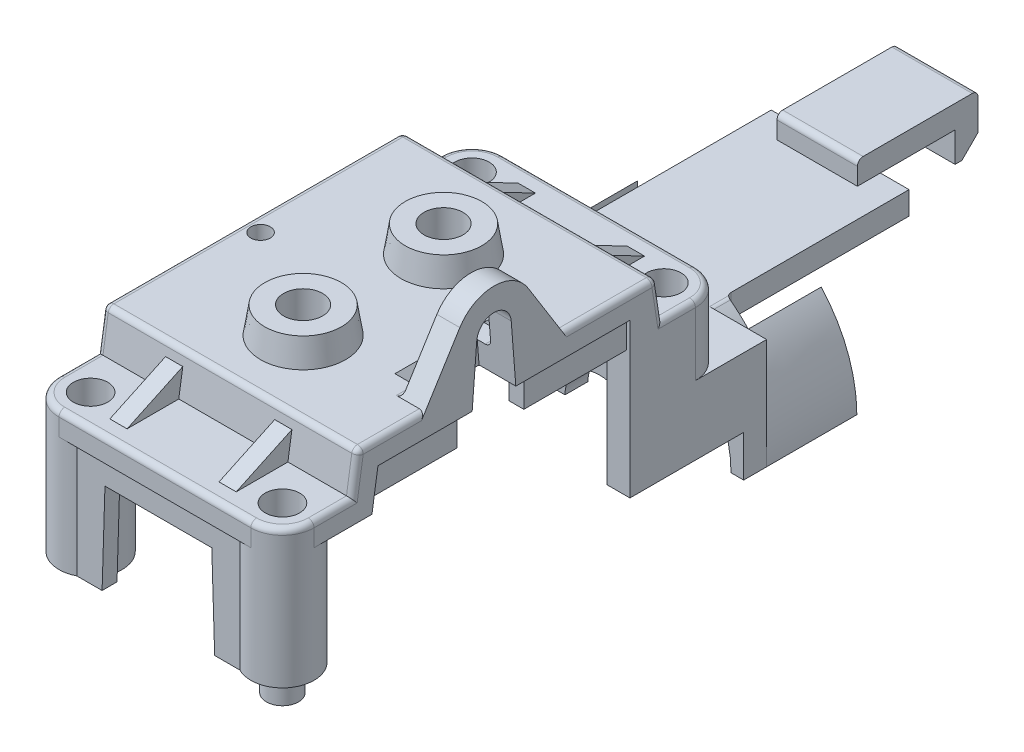
SolidWorks part; units mm, degrees
ref_plane "Front Plane" through (0, 0, 0) normal (0, 0, 1) x (1, 0, 0)
ref_plane "Top Plane" through (0, 0, 0) normal (0, 1, 0) x (1, 0, 0)
ref_plane "Right Plane" through (0, 0, 0) normal (1, 0, 0) x (0, 0, -1)
sketch "Sketch1" plane through (0, 0, 0) normal (0, 1, 0) x (1, 0, 0)
  line L1 (8.35, -16.6) -> (-8.35, -16.6) construction
  line L2 (8.35, -16.6) -> (8.35, 16.6) construction
  line L3 (8.35, 16.6) -> (-8.35, 16.6) construction
  line L4 (-8.35, -16.6) -> (-8.35, 16.6) construction
  line L5 (8.35, -16.6) -> (-8.35, 16.6) construction
  line L6 (8.35, 16.6) -> (-8.35, -16.6) construction
  circle A0 centre (-8.35, 16.6) radius 2.75
  circle A1 centre (8.35, 16.6) radius 2.75
  circle A2 centre (-8.35, -16.6) radius 2.75
  circle A3 centre (8.35, -16.6) radius 2.75
  point P0 (0, 0)
  dimension "D2" = 5.5
  dimension "D1" = 33.2
  dimension "D3" = 16.7
extrude "Boss-Extrude1" add sketch "Sketch1" along normal blind 10
sketch "Sketch2" plane through (0, 10, 0) normal (0, 1, 0) x (1, 0, 0)
  line L0 (-11.1, 16.6) -> (11.1, 16.6)
  line L1 (-11.1, -16.6) -> (11.1, -16.6)
  line L2 (-11.1, -16.6) -> (-11.1, -11.25)
  line L3 (-11.1, -11.25) -> (11.1, -11.25)
  line L4 (11.1, -16.6) -> (11.1, -11.25)
  line L5 (8.35, -19.35) -> (-8.35, -19.35)
  line L6 (8.35, -19.35) -> (8.35, -16.6)
  line L7 (8.35, -16.6) -> (-8.35, -16.6)
  line L8 (-8.35, -19.35) -> (-8.35, -16.6)
  line L9 (-11.1, 16.6) -> (-11.1, 11.75)
  line L10 (11.1, 16.6) -> (11.1, 11.75)
  line L11 (-11.1, 11.75) -> (11.1, 11.75)
  line L12 (-8.35, 19.35) -> (8.35, 19.35)
  line L13 (-8.35, 19.35) -> (-8.35, 16.6)
  line L14 (8.35, 19.35) -> (8.35, 16.6)
  line L15 (-8.35, 16.6) -> (8.35, 16.6)
  circle A0 centre (-8.35, -16.6) radius 2.75 construction
  circle A1 centre (8.35, -16.6) radius 2.75 construction
  arc A2 (-8.35, -19.35) -> (-11.1, -16.6) centre (-8.35, -16.6) cw
  arc A3 (8.35, -19.35) -> (11.1, -16.6) centre (8.35, -16.6) ccw
  circle A4 centre (-8.35, 16.6) radius 2.75 construction
  circle A5 centre (8.35, 16.6) radius 2.75 construction
  arc A6 (8.35, 19.35) -> (11.1, 16.6) centre (8.35, 16.6) cw
  arc A7 (-11.1, 16.6) -> (-8.35, 19.35) centre (-8.35, 16.6) cw
  point P32 (-8.35, 13.85)
  circle M5 centre (8.35, -16.6) radius 2.75
  dimension "D1" = 8.1
  dimension "D2" = 2.1
extrude "Boss-Extrude2" add sketch "Sketch2" along normal blind 2 contours A7 L0 L13 | L14 L12 L13 L0 | L9 L11 L10 L0 | A6 L14 L0 | L4 L3 L2 L1 M5 | L8 L5 L1 M5 | A2 L8 L1 | L6 L1 M5 | L1 M5 | L6 L1 M5 region at (-9.5171, 10, -17.7671) region at (0, 10, -14.175) region at (0, 10, -17.975) region at (9.5171, 10, -17.7671) region at (-0.928, 10, 13.7574) region at (-9.5171, 10, 17.7671) region at (-1.067, 10, 18.0059) region at (8.35, 10, 15.4329) region at (7.1829, 10, 17.7671) region at (9.5171, 10, 17.7671)
sketch "Sketch3" plane through (11.1, 0, 0) normal (1, 0, 0) x (0, 0, -1)
  line L0 (-11.25, 12) -> (-13.2267, 12.3044)
  line L1 (-11.25, 12) -> (-10.7733, 15.0956)
  line L2 (-13.2267, 12.3044) -> (-12.75, 15.4)
  line L3 (-10.7733, 15.0956) -> (-12.75, 15.4)
  line L4 (11.75, 12) -> (13.7267, 12.3044)
  line L5 (11.75, 12) -> (11.2733, 15.0956)
  line L6 (13.7267, 12.3044) -> (13.25, 15.4)
  line L7 (11.2733, 15.0956) -> (13.25, 15.4)
  line L8 (-12.75, 15.4) -> (13.25, 15.4)
  line L9 (-12.75, 15.4) -> (-12.75, 13.4)
  line L10 (13.25, 15.4) -> (13.25, 13.4)
  line L11 (-12.75, 13.4) -> (13.25, 13.4)
  line L12 (-11.25, 12) -> (-11.25, 10) construction
  line L13 (-11.25, 12) -> (-13.2736, 12)
  line L14 (-16.6, 12) -> (-11.25, 12) construction
  line L15 (11.75, 12) -> (13.7736, 12)
  line L17 (13.7736, 12) -> (13.7267, 12.3044)
  line L18 (-13.2736, 12) -> (-13.2267, 12.3044)
  line L19 (-13.2267, 12.3044) -> (-11.25, 12)
  line L20 (13.7267, 12.3044) -> (11.75, 12)
  line L21 (16.6, 12) -> (11.75, 12) construction
  line L22 (-16.6, 10) -> (-11.25, 10) construction
  point P0 (-11.0344, 13.4)
  point P21 (11.5344, 13.4)
  line M18 (-11.25, 12) -> (-16.6, 12)
  dimension "D1" = 5.4
  dimension "D2" = 26
extrude "Boss-Extrude4" add sketch "Sketch3" against normal up to surface (22.2 mm away) contours L1 L11 L5 L7 L8 L3 | L11 L9 L2 L0 L1 | L9 L11 L1 L3 | L18 L0 M18 | L11 L5 L4 L6 L10 | L5 L11 L10 L7 | L15 L17 L4 region at (11.1, 12.1015, 12.5834) region at (11.1, 12.9136, 12.1833) region at (11.1, 14.3493, 11.8487) region at (11.1, 14.4077, -0.25) region at (11.1, 12.9136, -12.6833) region at (11.1, 14.3493, -12.3487) region at (11.1, 12.1015, -13.0834) up to face at (-11.1, 11, 13.925)
sketch "Sketch4" plane through (11.1, 0, 0) normal (1, 0, 0) x (0, 0, -1)
  line L0 (-11.25, 10) -> (-11.25, 12)
  line L1 (-11.25, 12) -> (-11.558, 10)
  line L2 (-16.6, 10) -> (-11.25, 10) construction
  line L3 (-11.558, 10) -> (-11.25, 10)
  line L4 (11.75, 12) -> (11.75, 10)
  line L5 (11.75, 10) -> (12.058, 10)
  line L6 (16.6, 10) -> (11.75, 10) construction
  line L7 (12.058, 10) -> (11.75, 12)
  line L8 (11.75, 12) -> (11.5344, 13.4) construction
  line L9 (-11.25, 12) -> (-11.0344, 13.4) construction
extrude "Cut-Extrude1" cut sketch "Sketch4" against normal up to surface (22.2 mm away) up to face at (-11.1, 12.1143, -0.1786)
sketch "Sketch6" plane through (0, 0, 19.35) normal (0, 0, 1) x (1, 0, 0)
  line L0 (-8.35, 10) -> (8.35, 10)
  line L1 (-8.35, 10) -> (-8.35, 0)
  line L2 (8.35, 10) -> (8.35, 0)
  line L3 (-8.35, 0) -> (8.35, 0)
  line L4 (-4.65, 8) -> (4.65, 8)
  line L5 (-4.65, 8) -> (-4.9, 0)
  line L6 (4.65, 8) -> (4.9, 0)
  line L7 (-4.9, 0) -> (4.9, 0)
  line L8 (5.6, 0) -> (11.1, 0) construction
  point P13 (0, 8)
  point P14 (0, 0)
  point P15 (0, 0)
  line M9 (-8.35, 10) -> (8.35, 10)
  dimension "D1" = 2
  dimension "D2" = 9.3
  dimension "D3" = 9.8
extrude "Boss-Extrude5" add sketch "Sketch6" against normal blind 1.3 from offset 0.3 contours L4 L6 L3 L2 L1 L5 M9 region at (0, 9.8053, 19.35) offset against normal yes
sketch "Sketch7" plane through (0, 0, 0) normal (1, 0, 0) x (0, 0, -1)
  line L0 (-13.2736, 12) -> (-17.7736, 12)
  line L1 (-17.7736, 12) -> (-12.9235, 14.2732)
  line L2 (-12.9235, 14.2732) -> (-13.2736, 12)
  line L6 (-12.9235, 14.2732) -> (-12.75, 15.4) construction
  dimension "D1" = 4.5
  dimension "D2" = 2.3
extrude "Boss-Extrude6" add sketch "Sketch7" along normal blind 1.5 from offset 4
sketch "Sketch8" plane through (0, 0, 0) normal (1, 0, 0) x (0, 0, -1)
  line L0 (-13.2736, 12) -> (-12.9235, 14.2732)
  line L1 (-12.9235, 14.2732) -> (-17.7736, 12)
  line L2 (-17.7736, 12) -> (-13.2736, 12)
extrude "Boss-Extrude7" add sketch "Sketch8" against normal blind 1.5 from offset 4 offset against normal yes
sketch "Sketch10" plane through (0, 0, 0) normal (0, -1, 0) x (1, 0, 0)
  circle A0 centre (8.35, 16.6) radius 1.4
  dimension "D1" = 2.8
extrude "Boss-Extrude8" add sketch "Sketch10" along normal blind 2.3
sketch "Sketch9" plane through (0, 0, 0) normal (0, -1, 0) x (1, 0, 0)
  circle A0 centre (-8.35, 16.6) radius 1.5
  circle A1 centre (-8.35, -16.6) radius 1.5
  circle A2 centre (8.35, -16.6) radius 1.5
  dimension "D1" = 3
extrude "Cut-Extrude2" cut sketch "Sketch9" against normal up to surface (12 mm away) up to face at (0, 12, 15.9839)
sketch "Sketch11" plane through (0, 0, 0) normal (0, -1, 0) x (1, 0, 0)
  line L0 (11.1, -16.6) -> (9.1, -16.6)
  line L1 (11.1, -16.6) -> (11.1, -10.9)
  line L2 (9.1, -16.6) -> (9.1, -10.9)
  line L3 (11.1, -10.9) -> (9.1, -10.9)
  line L4 (-11.1, -16.6) -> (-9.1, -16.6)
  line L5 (-11.1, -16.6) -> (-11.1, -10.9)
  line L6 (-9.1, -16.6) -> (-9.1, -10.9)
  line L7 (-11.1, -10.9) -> (-9.1, -10.9)
  circle A0 centre (8.35, -16.6) radius 2.75 construction
  circle A2 centre (-8.35, -16.6) radius 2.75 construction
  dimension "D1" = 5.7
  dimension "D2" = 2
extrude "Boss-Extrude9" add sketch "Sketch11" against normal up to body separate body
sketch "Sketch12" plane through (0, 15.4, 0) normal (0, 1, 0) x (1, 0, 0)
  line L1 (-11.1, -12.75) -> (11.1, -12.75) construction
  line L2 (-11.1, 13.7736) -> (11.1, 13.7736) construction
  circle A0 centre (0, -6.45) radius 1.7 construction
  circle A1 centre (0, 5.7736) radius 1.7 construction
  circle A2 centre (0, -6.45) radius 3.7
  circle A3 centre (0, 5.7736) radius 3.7
  circle A4 centre (-8.35, -16.6) radius 1.5 construction
  point P4 (0, -8.15)
  point P5 (0, 0)
  point P10 (0, 7.4736)
  point P14 (0, -4.75)
  point P15 (0, 4.0736)
  dimension "D1" = 3.4
  dimension "D2" = 4.6
  dimension "D3" = 7.4
  dimension "D6" = 10.15
  dimension "D4" = 6.3
  dimension "D5" = 8.8236
extrude "Boss-Extrude10" add sketch "Sketch12" along normal blind 2.3 draft 9
sketch "Sketch13" plane through (0, 13.4, 0) normal (0, -1, 0) x (1, 0, 0)
  circle A0 centre (0, 6.45) radius 3.25
  dimension "D1" = 6.5
extrude "Boss-Extrude11" add sketch "Sketch13" along normal blind 3.1
sketch "Sketch14" plane through (0, 17.7, 0) normal (0, 1, 0) x (1, 0, 0)
  circle A0 centre (0, -6.45) radius 1.7
  circle A1 centre (0, 5.7736) radius 1.7
  circle A2 centre (0, -6.45) radius 1.7 construction
  circle A3 centre (0, 5.7736) radius 1.7 construction
extrude "Cut-Extrude3" cut sketch "Sketch14" against normal up to surface (7.4 mm away) up to face at (0, 10.3, 3.2)
sketch "Sketch15" plane through (0, 12, 0) normal (0, 1, 0) x (1, 0, 0)
  circle A0 centre (8.35, -16.6) radius 1.5
  circle A1 centre (-8.35, -16.6) radius 1.5 construction
  arc A2 (8.35, -19.35) -> (11.1, -16.6) centre (8.35, -16.6) ccw construction
extrude "Cut-Extrude4" cut sketch "Sketch15" against normal blind 10
sketch "Sketch16" plane through (0, 13.4, 0) normal (0, -1, 0) x (1, 0, 0)
  line L0 (11.1, 2.8344) -> (11.1, -0.9656)
  line L1 (11.1, 2.8344) -> (7.9, 2.8344)
  line L2 (11.1, -0.9656) -> (7.9, -0.9656)
  line L3 (7.9, 2.8344) -> (7.9, -0.9656)
  line L4 (11.1, 11.0344) -> (11.1, -10.9) construction
  dimension "D1" = 3.2
  dimension "D2" = 3.8
  dimension "D3" = 8.2
extrude "Cut-Extrude5" cut sketch "Sketch16" against normal up to surface (2 mm away) up to face at (0, 15.4, -9.4736)
sketch "Sketch17" plane through (11.1, 0, 0) normal (1, 0, 0) x (0, 0, -1)
  line L0 (-2.8344, 13.4) -> (0.9656, 13.4)
  line L1 (0.9656, 13.4) -> (0.5656, 18.5128)
  line L2 (0.5656, 18.5128) -> (-2.4344, 18.5128)
  line L3 (-2.4344, 18.5128) -> (-2.8344, 13.4)
  line L4 (-6.9344, 15.4) -> (-3.9076, 20.2507)
  line L5 (-12.75, 15.4) -> (-2.8344, 15.4) construction
  line L6 (5.0656, 15.4) -> (2.0388, 20.2507)
  line L7 (0.9656, 15.4) -> (13.25, 15.4) construction
  line L8 (-6.9344, 15.4) -> (-2.8344, 15.4)
  line L9 (-2.8344, 15.4) -> (-2.8344, 13.4)
  line L10 (0.9656, 13.4) -> (0.9656, 15.4)
  line L11 (0.9656, 15.4) -> (5.0656, 15.4)
  arc A0 (-2.4344, 18.5128) -> (0.5656, 18.5128) centre (-0.9344, 18.3954) cw
  arc A1 (-3.9076, 20.2507) -> (2.0388, 20.2507) centre (-0.9344, 18.3954) cw
  point P4 (-0.9344, 13.4)
  point P7 (-0.9344, 18.5128)
  point P11 (-0.9344, 19.9)
  point P21 (-0.9344, 21.9)
  line M7 (13.25, 15.4) -> (0.9656, 15.4)
  line M8 (0.9656, 15.4) -> (0.9656, 13.4)
  dimension "D1" = 6.5
  dimension "D2" = 3
  dimension "D3" = 12
  dimension "D4" = 2
extrude "Boss-Extrude12" add sketch "Sketch17" against normal blind 2 contours A1 L4 L8 L9 L3 A0 L1 L6 M8 M7 region at (11.1, 14.4, 2.8197)
sketch "Sketch18" plane through (9.1, 0, 0) normal (-1, 0, 0) x (0, 0, 1)
  line L0 (2.8344, 13.4) -> (2.8344, 15.4)
  line L1 (2.8344, 15.4) -> (2.6779, 15.4)
  line L2 (2.6779, 15.4) -> (2.8344, 13.4)
  line L3 (-0.9656, 13.4) -> (-0.9656, 15.4)
  line L4 (-0.9656, 15.4) -> (-0.8091, 15.4)
  line L5 (-0.8091, 15.4) -> (-0.9656, 13.4)
  line L6 (-0.9656, 13.4) -> (-0.5656, 18.5128) construction
  line L7 (2.4344, 18.5128) -> (2.8344, 13.4) construction
extrude "Boss-Extrude13" add sketch "Sketch18" along normal up to surface (1.2 mm away) up to face at (7.9, 14.4, 0.9344)
ref_plane "Plane1" through (0, 0, 0.9344) normal (0, 0, 1) x (1, 0, 0)
sketch "Sketch19" plane through (0, 0, 0.9344) normal (0, 0, 1) x (1, 0, 0)
  line L0 (9.1, 15.4) -> (6.9, 15.4)
  line L1 (6.9, 15.4) -> (9.1, 17.6)
  line L2 (9.1, 17.6) -> (9.1, 15.4)
  dimension "D1" = 2.2
extrude "Boss-Extrude14" add sketch "Sketch19" along normal blind 0.55 and the other way blind 0.55 from offset 3.87
sketch "Sketch20" plane through (0, 0, 0.9344) normal (0, 0, 1) x (1, 0, 0)
  line L0 (9.1, 15.4) -> (9.1, 17.6)
  line L1 (9.1, 17.6) -> (6.9, 15.4)
  line L2 (6.9, 15.4) -> (9.1, 15.4)
extrude "Boss-Extrude15" add sketch "Sketch20" against normal blind 0.55 and the other way blind 0.55 from offset 3.87 offset against normal yes
sketch "Sketch22" plane through (11.1, 0, 0) normal (1, 0, 0) x (0, 0, -1)
  line L0 (-11.0344, 13.4) -> (-11.404, 11)
  line L1 (-11.558, 10) -> (-11.0344, 13.4) construction
  line L2 (-11.404, 11) -> (-3.8344, 11)
  line L3 (-3.8344, 11) -> (-3.8344, 13.4)
  line L4 (-11.0344, 13.4) -> (-2.8344, 13.4) construction
  line L5 (-3.8344, 13.4) -> (-11.0344, 13.4)
  line L6 (10.9, 13.4) -> (1.9656, 13.4)
  line L7 (0.9656, 13.4) -> (10.9, 13.4) construction
  line L8 (1.9656, 13.4) -> (1.9656, 11)
  line L9 (1.9656, 11) -> (10.9, 11)
  line L10 (10.9, 13.4) -> (10.9, 0) construction
  line L11 (10.9, 11) -> (10.9, 13.4)
  dimension "D1" = 1
  dimension "D2" = 1
  dimension "D3" = 2.4
extrude "Boss-Extrude17" add sketch "Sketch22" against normal blind 1.3 from offset 0.3 offset against normal yes
sketch "Sketch23" plane through (-11.1, 0, 0) normal (-1, 0, 0) x (0, 0, 1)
  line L0 (16.6, 10) -> (11.558, 10)
  line L1 (16.6, 10) -> (11.558, 10) construction
  line L2 (11.558, 10) -> (11.0344, 13.4)
  line L3 (11.0344, 13.4) -> (-10.9, 13.4)
  line L4 (-10.9, 13.4) -> (-10.9, 11.9)
  line L5 (-10.9, 13.4) -> (-10.9, 0) construction
  line L6 (-10.9, 11.9) -> (-2.4, 11.9)
  line L7 (-2.4, 11.9) -> (-1.9956, 0)
  line L8 (-1.9956, 0) -> (3.1044, 0)
  line L9 (3.1044, 0) -> (3.4544, 10.3)
  line L10 (3.4544, 10.3) -> (9.4882, 10.3)
  line L11 (9.4882, 10.3) -> (9.9348, 7.4)
  line L12 (9.9348, 7.4) -> (12.35, 7.4)
  line L13 (12.35, 7.4) -> (12.65, 0)
  line L14 (12.65, 0) -> (16.6, 0)
  line L15 (16.6, 0) -> (16.6, 10)
  line L16 (-10.9, 0) -> (-16.6, 0) construction
  line L17 (12.75, 15.4) -> (-13.25, 15.4) construction
  line L19 (3.4544, 10.3) -> (-2.3456, 10.3) construction
  point P9 (0.5544, 10.3)
  point P27 (0.5544, 0)
  point P29 (19.35, 12)
  dimension "D1" = 3.5
  dimension "D2" = 5.1
  dimension "D3" = 8
  dimension "D4" = 7
  dimension "D5" = 6.7
  dimension "D6" = 5.8
  dimension "D7" = 5.1
  dimension "D8" = 8.5
  dimension "D9" = 2
  dimension "D10" = 9.5456
extrude "Boss-Extrude18" add sketch "Sketch23" against normal blind 1.3 from offset 0.3 offset against normal yes
ref_plane "Plane2" through (-9.85, 0, 16.6) normal (0, 0, -1) x (-1, 0, 0)
sketch "Sketch25" plane through (0, 0, 0) normal (0, -1, 0) x (1, 0, 0)
  circle A0 centre (-8.35, 16.6) radius 1.5
  arc A1 (-9.5, 15.6369) -> (-9.85, 16.6) centre (-8.35, 16.6) ccw construction
extrude "Cut-Extrude6" cut sketch "Sketch25" against normal up to surface (12 mm away) up to face at (8.35, 12, 18.1)
sketch "Sketch26" plane through (0, 0, 0) normal (0, -1, 0) x (1, 0, 0)
  line L0 (-11.1, 11.0344) -> (-11.1, -10.9) construction
  line L1 (-10.8, -1.9956) -> (-10.8, 3.1044) construction
  circle A0 centre (-9.6, 0.5544) radius 1.5
  point P4 (-10.8, 0.5544)
  dimension "D1" = 3
extrude "Boss-Extrude19" add sketch "Sketch26" against normal up to surface (13.4 mm away) up to face at (0, 13.4, -7.4736)
sketch "Sketch27" plane through (0, 0, 0) normal (0, -1, 0) x (1, 0, 0)
  circle A0 centre (-9.6, 0.5544) radius 0.7
  arc A1 (-9.5, -0.9423) -> (-9.5, 2.051) centre (-9.6, 0.5544) ccw construction
  dimension "D1" = 1.4
extrude "Boss-Extrude20" add sketch "Sketch27" along normal blind 2.5
sketch "Sketch28" plane through (0, 15.4, 0) normal (0, 1, 0) x (1, 0, 0)
  circle A0 centre (-9.6, -0.5544) radius 0.85
  circle A1 centre (-9.6, -0.5544) radius 0.7 construction
  dimension "D1" = 1.7
extrude "Cut-Extrude8" cut sketch "Sketch28" against normal blind 1.2
sketch "Sketch29" plane through (0, 10, 0) normal (0, -1, 0) x (1, 0, 0)
  line L2 (8.35, -13.85) -> (8.35, -13.35)
  line L3 (5.6, -16.6) -> (5.1, -16.6)
  line L4 (-5.1, -16.6) -> (-5.6, -16.6)
  line L5 (-8.35, -13.35) -> (-8.35, -13.85)
  line L6 (8.35, -13.85) -> (8.35, -13.35) construction
  line L7 (8.35, -13.85) -> (8.85, -13.85) construction
  line L8 (8.35, -13.35) -> (8.85, -13.35) construction
  line L9 (8.85, -13.85) -> (8.85, -13.35) construction
  line L10 (5.6, -16.6) -> (5.1, -16.6) construction
  line L11 (5.6, -16.6) -> (5.6, -17.1) construction
  line L12 (5.1, -16.6) -> (5.1, -17.1) construction
  line L13 (5.6, -17.1) -> (5.1, -17.1) construction
  line L14 (-8.35, -13.85) -> (-8.35, -13.35) construction
  line L15 (-8.35, -13.85) -> (-8.85, -13.85) construction
  line L16 (-8.35, -13.35) -> (-8.85, -13.35) construction
  line L17 (-8.85, -13.85) -> (-8.85, -13.35) construction
  line L18 (-5.6, -16.6) -> (-5.1, -16.6) construction
  line L19 (-5.6, -16.6) -> (-5.6, -17.1) construction
  line L20 (-5.1, -16.6) -> (-5.1, -17.1) construction
  line L21 (-5.6, -17.1) -> (-5.1, -17.1) construction
  arc A0 (8.35, -13.85) -> (5.6, -16.6) centre (8.35, -16.6) ccw
  arc A1 (9.1, -13.9542) -> (8.35, -19.35) centre (8.35, -16.6) ccw construction
  arc A2 (-5.6, -16.6) -> (-8.35, -13.85) centre (-8.35, -16.6) ccw
  arc A3 (-8.35, -19.35) -> (-9.1, -13.9542) centre (-8.35, -16.6) ccw construction
  arc A4 (8.35, -13.35) -> (5.1, -16.6) centre (8.35, -16.6) ccw
  arc A5 (-5.1, -16.6) -> (-8.35, -13.35) centre (-8.35, -16.6) ccw
  dimension "D1" = 0.5
extrude "Boss-Extrude21" add sketch "Sketch29" along normal offset from surface (10.3 mm away) 0.3 up to face at (8.35, 0, -18.1) offset beyond the face yes
sketch "Sketch30" plane through (0, 10, 0) normal (0, -1, 0) x (1, 0, 0)
  line L0 (-8.35, -19.35) -> (8.35, -19.35) construction
  line L1 (5.9542, -17.95) -> (-5.9542, -17.95)
  line L2 (-8.35, -19.35) -> (8.35, -19.35)
  arc A0 (8.35, -19.35) -> (5.9542, -17.95) centre (8.35, -16.6) cw
  arc A1 (5.6, -16.6) -> (8.35, -19.35) centre (8.35, -16.6) ccw construction
  arc A2 (-8.35, -19.35) -> (-5.9542, -17.95) centre (-8.35, -16.6) ccw
  arc A3 (-8.35, -19.35) -> (-5.6, -16.6) centre (-8.35, -16.6) ccw construction
  dimension "D1" = 1.4
extrude "Boss-Extrude22" add sketch "Sketch30" along normal blind 6
sketch "Sketch31" plane through (0, 0, 0) normal (0, -1, 0) x (1, 0, 0)
  line L0 (11.1, -16.6) -> (9.1, -16.6)
  line L1 (11.1, -16.6) -> (11.1, -22.8)
  line L2 (9.1, -16.6) -> (9.1, -22.8)
  line L3 (11.1, -22.8) -> (9.1, -22.8)
  line L4 (-11.1, -16.6) -> (-9.1, -16.6)
  line L5 (-11.1, -16.6) -> (-11.1, -22.8)
  line L6 (-9.1, -16.6) -> (-9.1, -22.8)
  line L7 (-11.1, -22.8) -> (-9.1, -22.8)
  line L8 (9.1, -10.9) -> (9.1, -13.9542) construction
  line L9 (-9.1, -13.9542) -> (-9.1, -10.9) construction
  line L10 (11.1, -10.9) -> (9.1, -10.9) construction
  arc A0 (11.1, -16.6) -> (9.1, -19.2458) centre (8.35, -16.6) cw
  arc A1 (-11.1, -16.6) -> (-9.1, -19.2458) centre (-8.35, -16.6) ccw
  arc A2 (-11.1, -16.6) -> (-5.6, -16.6) centre (-8.35, -16.6) ccw construction
  arc A3 (5.6, -16.6) -> (11.1, -16.6) centre (8.35, -16.6) ccw construction
  arc M8 (5.6, -16.6) -> (11.1, -16.6) centre (8.35, -16.6) ccw
  dimension "D1" = 11.9
extrude "Boss-Extrude23" add sketch "Sketch31" against normal blind 6 contours L3 L1 L2 M8 | A1 L5 L7 L6 region at (10.1773, 0, -20.6335) region at (-10.1773, 0, -20.6335)
sketch "Sketch32" plane through (0, 6, 0) normal (0, 1, 0) x (1, 0, 0)
  line L0 (-9.1, 22.8) -> (9.1, 22.8)
  line L1 (-9.1, 22.8) -> (-9.1, 19.2458)
  line L2 (9.1, 22.8) -> (9.1, 19.2458)
  line L3 (-9.1, 19.2458) -> (9.1, 19.2458)
  line L4 (9.1, 19.2458) -> (9.1, 22.8) construction
  line L5 (-6, 22.8) -> (6, 22.8)
  line L6 (-6, 22.8) -> (-6, 40.3)
  line L7 (-6, 40.3) -> (6, 40.3)
  line L8 (6, 22.8) -> (6, 40.3)
  arc A0 (11.1, 16.6) -> (9.1, 19.2458) centre (8.35, 16.6) ccw construction
  point P12 (0, 22.8)
  point P13 (0, 22.8)
  line M10 (9.1, 22.8) -> (9.1, 19.2458)
  dimension "D1" = 17.5
  dimension "D2" = 12
extrude "Boss-Extrude24" add sketch "Sketch32" against normal blind 2 contours L1 L3 L0 M10 | L0 L8 L7 L6 region at (0, 6, -21.0229) region at (0, 6, -31.55)
sketch "Sketch33" plane through (0, 4, 0) normal (0, -1, 0) x (1, 0, 0)
  line L0 (8.2, -19.3459) -> (6.3794, -18.5181)
  line L1 (8.2, -19.3459) -> (7.2888, -21.35)
  line L2 (6.3794, -18.5181) -> (5.4681, -20.5222)
  line L3 (7.2888, -21.35) -> (5.4681, -20.5222)
  line L4 (-8.2, -19.3459) -> (-6.3794, -18.5181)
  line L5 (-8.2, -19.3459) -> (-7.2888, -21.35)
  line L6 (-6.3794, -18.5181) -> (-5.4681, -20.5222)
  line L7 (-7.2888, -21.35) -> (-5.4681, -20.5222)
  line L8 (7.2888, -21.35) -> (-7.2888, -21.35)
  line L9 (7.2888, -21.35) -> (7.2888, -19.35)
  line L10 (-7.2888, -21.35) -> (-7.2888, -19.35)
  line L11 (7.2888, -19.35) -> (-7.2888, -19.35)
  line L12 (5.9542, -17.95) -> (-5.9542, -17.95) construction
  arc A0 (5.9542, -17.95) -> (9.1, -19.2458) centre (8.35, -16.6) ccw construction
  arc A1 (-9.1, -19.2458) -> (-5.9542, -17.95) centre (-8.35, -16.6) ccw construction
  arc M13 (-5.9542, -17.95) -> (-9.1, -19.2458) centre (-8.35, -16.6) cw
  dimension "D1" = 2
  dimension "D2" = 16.4
  dimension "D3" = 3.4
  dimension "D4" = 2.8319
extrude "Boss-Extrude25" add sketch "Sketch33" along normal up to surface (4 mm away) contours L2 L11 L6 L7 L8 L3 | L9 L11 L2 L3 | L11 L6 L5 L10 M13 | L6 L11 L10 L7 | L3 L2 L0 L1 region at (0, 4, -20.3796) region at (6.5561, 4, -20.212) region at (-6.5561, 4, -20.212) region at (-7.7117, 4, -20.3331) up to face at (8.35, 0, -18.1)
sketch "Sketch34" plane through (0, 0, -21.35) normal (0, 0, -1) x (-1, 0, 0)
  line L0 (-5.8, 0) -> (5.8, 0)
  line L1 (7.2888, 0) -> (-7.2888, 0) construction
  line L2 (5.8, 0) -> (5.6, -3.5)
  line L3 (5.6, -3.5) -> (-5.6, -3.5)
  line L4 (-5.6, -3.5) -> (-5.8, 0)
  line L5 (-7.2888, 4) -> (7.2888, 4) construction
  circle A0 centre (0, -3.5) radius 3
  point P4 (0, -3.5)
  point P7 (0, 0)
  point P9 (0, 0)
  line M6 (-7.2888, 0) -> (7.2888, 0)
  dimension "D3" = 6
  dimension "D1" = 11.6
  dimension "D2" = 11.2
  dimension "D4" = 7.5
extrude "Boss-Extrude26" add sketch "Sketch34" against normal up to surface (2 mm away) contours A0 L4 L3 M6 region at (0, -0.1212, -21.35) up to face at (0, 2, -19.35)
sketch "Sketch35" plane through (0, 0, -22.8) normal (0, 0, -1) x (-1, 0, 0)
  line L0 (-11.1, 0) -> (-11.1, -3.6) construction
  line L1 (-11.1, 6) -> (-6, 6) construction
  line L2 (6.3, 6) -> (-6.3, 6)
  line L4 (6, 6) -> (-6, 6) construction
  line L5 (-11.1, -3.6) -> (-10, -3.6)
  line L6 (0, 8.06) -> (0, 6.4) construction
  line L7 (10, -3.6) -> (11.1, -3.6)
  line L8 (-6, 6) -> (-6, 4)
  line L9 (-6, 4) -> (-6.4992, 4)
  line L10 (6.3, 6) -> (6, 6)
  line L11 (6, 6) -> (6, 4)
  line L12 (6, 4) -> (6.4992, 4)
  line L13 (9.1, 4) -> (6, 4) construction
  ellipse E0 centre (0, -3.6) end of major axis (0, 8.06) minor radius 11.1
  ellipse E1 centre (0, -3.6) end of major axis (-10, -3.6) minor radius 10
  point P21 (0, 6)
  line M6 (-11.1, 0) -> (-9.1, 0)
  line M7 (-9.1, 0) -> (-9.1, 4)
  line M8 (-9.1, 4) -> (-6, 4)
  line M9 (-6, 4) -> (-6, 6)
  line M10 (-6, 6) -> (-11.1, 6)
  dimension "D1" = 9.6
  dimension "D2" = 20
  dimension "D3" = 20
  dimension "D4" = 12.6
extrude "Boss-Extrude27" add sketch "Sketch35" along normal blind 1.5 contours E1 L7 E0 L2 L11 | L12 E1 L11 | E1 L8 E0 M10 M8 | E1 E0 L5 M8 M7 M6 | E0 M7 M6 | E1 M9 M8 | E1 E0 L5 M6 region at (-8.8827, 1.4706, -22.8) region at (-6.1682, 4.1348, -22.8) region at (10.3444, -1.7668, -22.8) region at (6.8778, 4.7812, -22.8) region at (9.629, 1.1083, -22.8) region at (8.247, 2.8762, -22.8) region at (6.1682, 4.1348, -22.8)
sketch "Sketch36" plane through (0, 0, -22.8) normal (0, 0, 1) x (1, 0, 0)
  line L0 (11.1, -3.6) -> (11.1, 0)
  line L1 (11.1, 0) -> (9.1, 0)
  line L2 (9.1, 0) -> (9.1, 4)
  line L3 (9.1, 4) -> (6.4992, 4)
  line L6 (10, -3.6) -> (11.1, -3.6)
  line L7 (-6.4992, 4) -> (-9.1, 4)
  line L8 (-9.1, 4) -> (-9.1, 0)
  line L9 (-9.1, 0) -> (-11.1, 0)
  line L10 (-11.1, 0) -> (-11.1, -3.6)
  line L11 (-10, -3.6) -> (-11.1, -3.6)
  line L12 (-10, -3.6) -> (-11.1, -3.6) construction
  ellipse E0 centre (0, -3.6) end of major axis (10, -3.6) minor radius 10 (-9.3295, 0) -> (-10, -3.6) ccw construction
  ellipse E1 centre (0, -3.6) end of major axis (0, 6.4) minor radius 10 (10, -3.6) -> (6.4992, 4) ccw
  ellipse E2 centre (0, -3.6) end of major axis (-10, -3.6) minor radius 10 (-10, -3.6) -> (-6.4992, 4) cw
  ellipse M9 centre (0, -3.6) end of major axis (0, 8.06) minor radius 11.1 (9.1, 3.0768) -> (8.4181, 4) ccw
  line M10 (8.4181, 4) -> (6.4992, 4)
  ellipse M11 centre (0, -3.6) end of major axis (10, -3.6) minor radius 10 (6.4992, 4) -> (9.1, 0.5461) cw
  line M15 (9.1, 0.5461) -> (9.1, 3.0768)
extrude "Boss-Extrude28" add sketch "Sketch36" along normal blind 2 contours E1 L6 L0 L1 | L11 E2 L9 L10 | L8 E2 L7 | M15 M9 M10 M11 | L2 L3 M9 region at (10.4248, -1.6487, -22.8) region at (8.247, 2.8762, -22.8) region at (8.8766, 3.6976, -22.8) region at (-8.2973, 2.9418, -22.8) region at (-10.4248, -1.6487, -22.8)
sketch "Sketch37" plane through (0, 0, -24.3) normal (0, 0, -1) x (-1, 0, 0)
  line L0 (-11.1, -3.6) -> (-10, -3.6)
  line L1 (-11.1, -3.6) -> (-10, -3.6) construction
  line L2 (11.1, -3.6) -> (10, -3.6)
  line L3 (-8, 4.483) -> (-8, 2.4)
  line L4 (8, 4.483) -> (8, 2.4)
  line L6 (-6, 4) -> (-6, 6) construction
  ellipse E0 centre (0, -3.6) end of major axis (-10, -3.6) minor radius 10 (-6.4992, 4) -> (-10, -3.6) ccw construction
  ellipse E1 centre (0, -3.6) end of major axis (0, -13.6) minor radius 10
  ellipse E2 centre (0, -3.6) end of major axis (0, 8.06) minor radius 11.1
  ellipse E3 centre (0, -3.6) end of major axis (-10, -3.6) minor radius 10 (10, -3.6) -> (6.4992, 4) ccw construction
  ellipse M7 centre (0, -3.6) end of major axis (0, 8.06) minor radius 11.1 (-6.3, 6) -> (-11.1, -3.6) ccw
  line M8 (-11.1, -3.6) -> (-10, -3.6)
  ellipse M9 centre (0, -3.6) end of major axis (-10, -3.6) minor radius 10 (-10, -3.6) -> (-6.4992, 4) cw
  dimension "D1" = 2
extrude "Boss-Extrude29" add sketch "Sketch37" along normal blind 6.35 contours L3 M7 M8 M9 | L2 E2 L4 E1 region at (9.6612, 0.2308, -24.3) region at (-9.6612, 0.2308, -24.3)
sketch "Sketch38" plane through (0, 0, 0) normal (1, 0, 0) x (0, 0, -1)
  line L0 (48.8, 3.4) -> (48.8, 4.8)
  line L1 (38.3, 6) -> (48.8, 6)
  line L2 (38.3, 6) -> (38.3, 8)
  line L3 (38.3, 8) -> (48.8, 8)
  line L4 (48.8, 6) -> (48.8, 8)
  line L5 (48.8, 6) -> (46.8, 6)
  line L6 (48.8, 6) -> (48.8, 3.4)
  line L7 (48.8, 3.4) -> (46.8, 3.4)
  line L8 (46.8, 6) -> (46.8, 3.4)
  line L9 (48.8, 4.8) -> (47.4, 3.4)
  line L10 (47.4, 3.4) -> (48.8, 3.4)
  line L11 (40.3, 4) -> (40.3, 6) construction
  line L12 (38.3, 6) -> (40.3, 6)
  dimension "D1" = 10.5
  dimension "D2" = 4.6
  dimension "D3" = 3.2
extrude "Boss-Extrude30" add sketch "Sketch38" along normal mid plane 7 contours L1 L4 L3 L2 | L9 L6 L1 L8 L7 region at (0, 4.8935, -47.6761) region at (0, 7, -43.55)
sketch "Sketch39" plane through (4, 0, 0) normal (-1, 0, 0) x (0, 0, 1)
  line L0 (-13.4235, 14.2732) -> (-13.7736, 12)
  line L1 (-13.7736, 12) -> (-17.7736, 12)
  line L2 (-17.7736, 12) -> (-13.4235, 14.2732)
  line L3 (-13.7736, 12) -> (-13.25, 15.4) construction
  line L4 (-15.1, 12) -> (-18.1, 12) construction
  line L5 (17.7736, 12) -> (19.35, 12) construction
  line L8 (-19.35, 12) -> (-17.7736, 12) construction
extrude "Boss-Extrude31" add sketch "Sketch39" against normal up to surface (1.5 mm away) up to face at (5.5, 12.7577, 14.6569)
sketch "Sketch40" plane through (-5.5, 0, 0) normal (-1, 0, 0) x (0, 0, 1)
  line L0 (-13.7736, 12) -> (-13.4235, 14.2732)
  line L1 (-13.4235, 14.2732) -> (-17.7736, 12)
  line L2 (-17.7736, 12) -> (-13.7736, 12)
extrude "Boss-Extrude32" add sketch "Sketch40" against normal up to surface (1.5 mm away) up to face at (-4, 12.7577, 14.6569)
fillet "Fillet1" radius 0.5 27 edges at (11.1, 12, 14.9368) (10.2945, 12, 18.5445) (-11.1, 12, 14.9368) (-10.2945, 12, 18.5445) (0, 12, 19.35) (-11.1, 12, -15.1868) (-10.2945, 12, -18.5445) (11.1, 12, -15.1868) (10.2945, 12, -18.5445) (0, 12, -19.35) (11.1, 15.4, -9.1578) (0, 15.4, -13.25) (11.1, 15.4, 9.8422) (-11.1, 15.4, -0.25) (-11.1, 13.7, 13.0118) (0, 15.4, 12.75) (11.1, 13.7, 13.0118) (-11.1, 13.7, -13.5118) (11.1, 13.7, -13.5118) (9.1, 15.4, -4.2756) (9.1, 15.4, -1.5974) (9.1, 15.4, 3.4662) (9.1, 15.4, 6.1444) (0, 8, -48.8) (0, 8, -38.3) (-6, 5, -24.3) (6, 5, -24.3)
fillet "Fillet2" radius 0.5 2 edges at (-6.3, 6, -23.5709) (6.3, 6, -23.5709)
sketch "Sketch41" plane through (0, 0, -22.8) normal (0, 0, -1) x (-1, 0, 0)
  line L0 (-9.3295, 0) -> (-9.1, 0)
  line L1 (-9.1, 0) -> (-9.1, 0.5461)
  line L4 (9.1, 0) -> (9.3295, 0)
  line L7 (9.1, 0.5461) -> (9.1, 0)
  line L8 (9.1, 0.5461) -> (9.1, 0) construction
  arc A0 (-9.3295, 0) -> (-9.1, 0.5461) centre (0, -3.6) cw
  arc A1 (-9.1, 0.5461) -> (-9.3295, 0) centre (0, -3.6) ccw construction
  arc A2 (9.3295, 0) -> (9.1, 0.5461) centre (0, -3.6) ccw
  arc A3 (9.3295, 0) -> (9.1, 0.5461) centre (0, -3.6) ccw construction
  ellipse M1 centre (0, -3.6) end of major axis (-10, -3.6) minor radius 10 (9.3295, 0) -> (9.1, 0.5461) ccw
  line M2 (9.1, 0.5461) -> (9.1, 0)
  line M3 (9.1, 0) -> (9.3295, 0)
extrude "Cut-Extrude9" cut sketch "Sketch41" against normal up to surface (2 mm away) contours M3 M1 M2 | L0 L1 region at (9.1776, 0.1845, -22.8) region at (-9.1776, 0.1845, -22.8) up to face at (10.4239, -1.7923, -20.8)
